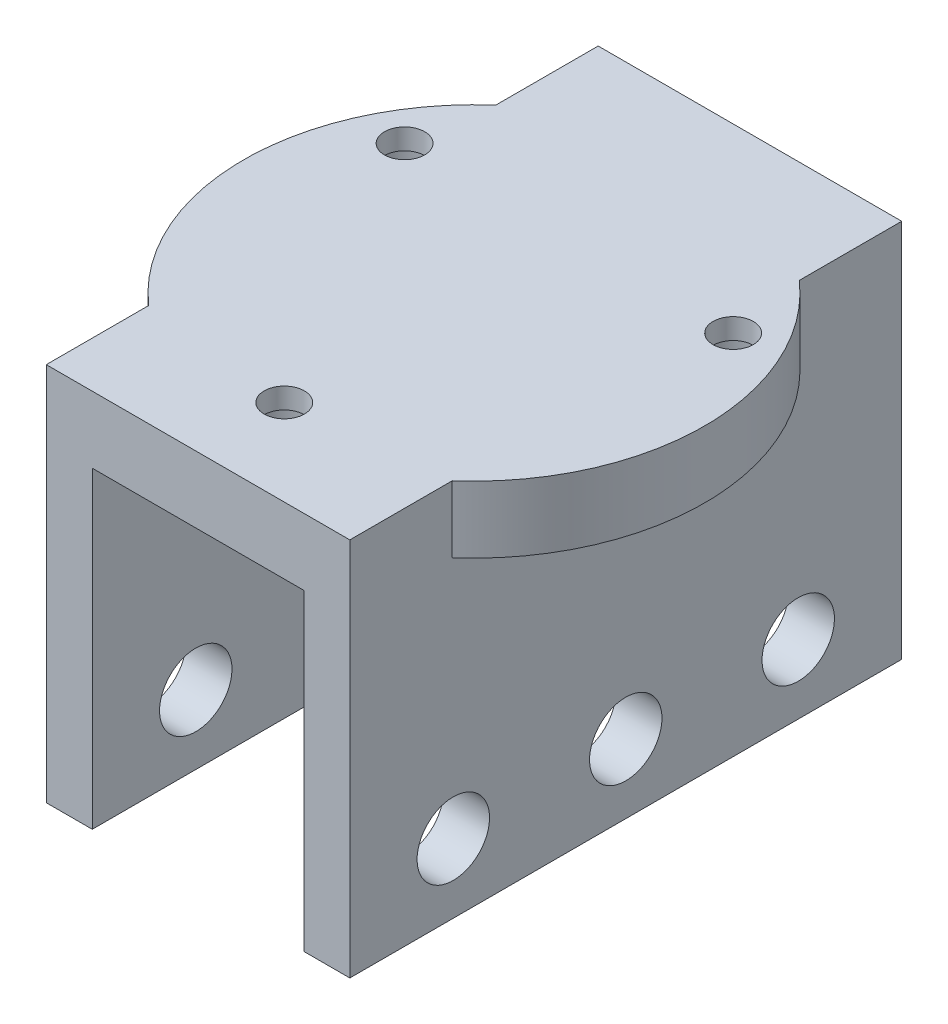
SolidWorks part; units mm, degrees
ref_plane "前基準面" through (0, 0, 0) normal (0, 0, 1) x (1, 0, 0)
ref_plane "上基準面" through (0, 0, 0) normal (0, 1, 0) x (1, 0, 0)
ref_plane "右基準面" through (0, 0, 0) normal (1, 0, 0) x (0, 0, -1)
sketch "草圖1" plane through (0, 0, 0) normal (0, 0, 1) x (1, 0, 0)
  line L0 (0, 0) -> (0, 33)
  line L5 (0, 33) -> (26.4, 33)
  line L6 (26.4, 33) -> (26.4, 0)
  line L12 (26.4, 0) -> (22.4, 0)
  line L13 (22.4, 0) -> (22.4, 27.2)
  line L14 (22.4, 27.2) -> (4, 27.2)
  line L15 (4, 27.2) -> (4, 0)
  line L16 (4, 0) -> (0, 0)
  dimension "D1" = 27.2
  dimension "D2" = 33
  dimension "D3" = 4
  dimension "D4" = 4
  dimension "D5" = 26.4
extrude "填料-伸長1" add sketch "草圖1" along normal mid plane 48
sketch "草圖2" plane through (0, 27.2, 0) normal (0, -1, 0) x (1, 0, 0)
  line L0 (13.2, 0) -> (20.3284, 0) construction
  line L2 (13.2, 24) -> (13.2, 22.7227) construction
  line L3 (4, 24) -> (22.4, 24) construction
  circle A0 centre (13.2, 0) radius 10 construction
  circle A1 centre (7.7199, 5.4801) radius 1.6
  circle A2 centre (18.6801, 5.4801) radius 1.6
  circle A3 centre (18.6801, -5.4801) radius 1.6
  circle A4 centre (7.7199, -5.4801) radius 1.6
  point P13 (13.2, 0)
  dimension "D1" = 20
  dimension "D2" = 3.2
  dimension "D3" = 7.75
  dimension "D4" = 4
extrude "除料-伸長1" [suppressed] cut sketch "草圖2" against normal through all
sketch "草圖3" plane through (26.4, 0, 0) normal (1, 0, 0) x (0, 0, -1)
  line L0 (-24, 0) -> (24, 0) construction
  line L1 (0, 0) -> (0, 16.3853) construction
  circle A0 centre (0, 6) radius 3.15
  circle A1 centre (15, 6) radius 3.15
  circle A2 centre (-15, 6) radius 3.15
  dimension "D1" = 6.3
  dimension "D2" = 6
  dimension "D3" = 15
extrude "除料-伸長2" cut sketch "草圖3" against normal up to surface (26.4 mm away) up to face at (0, 16.5, 0)
sketch "草圖4" plane through (0, 33, 0) normal (0, 1, 0) x (1, 0, 0)
  line L1 (0, -24) -> (0, 24) construction
  line L2 (26.4, -24) -> (0, -24) construction
  circle A0 centre (13.2, 0) radius 20.05
  point P8 (0, 0)
  point P11 (13.2, -24)
  point P16 (13.2, 0)
  dimension "D1" = 40.1
extrude "填料-伸長2" add sketch "草圖4" against normal up to surface (5.8 mm away) up to face at (13.2, 27.2, 0)
sketch "草圖5" plane through (0, 33, 0) normal (0, 1, 0) x (1, 0, 0)
  circle A0 centre (13.2, -16.5) radius 1.75
  arc A1 (26.4, -15.0918) -> (26.4, 15.0918) centre (13.2, 0) ccw construction
  circle A2 centre (-1.0894, 8.25) radius 1.75
  circle A3 centre (27.4894, 8.25) radius 1.75
  circle A4 centre (13.2, 0) radius 4.1759 construction
  point P11 (13.2, 0)
  dimension "D1" = 3.5
  dimension "D2" = 16.5
  dimension "D3" = 3
extrude "除料-伸長3" cut sketch "草圖5" against normal up to surface (5.8 mm away) up to face at (29.825, 27.2, 0)
sketch "草圖6" plane through (0, 27.2, 0) normal (0, -1, 0) x (1, 0, 0)
  circle A0 centre (-1.0894, -8.25) radius 3.1
  circle A1 centre (13.2, 16.5) radius 3.1
  circle A2 centre (27.4894, -8.25) radius 3.1
  dimension "D1" = 6.2
extrude "除料-伸長4" cut sketch "草圖6" against normal blind 4
extrude "除料-伸長5" cut sketch "草圖6<3>" along normal blind 6 contours A0 | A2 region at (-1.0894, 27.2, -8.25)
sketch "草圖6<3>" plane through (0, 27.2, 0) normal (0, -1, 0) x (1, 0, 0) same geometry as "草圖6"
